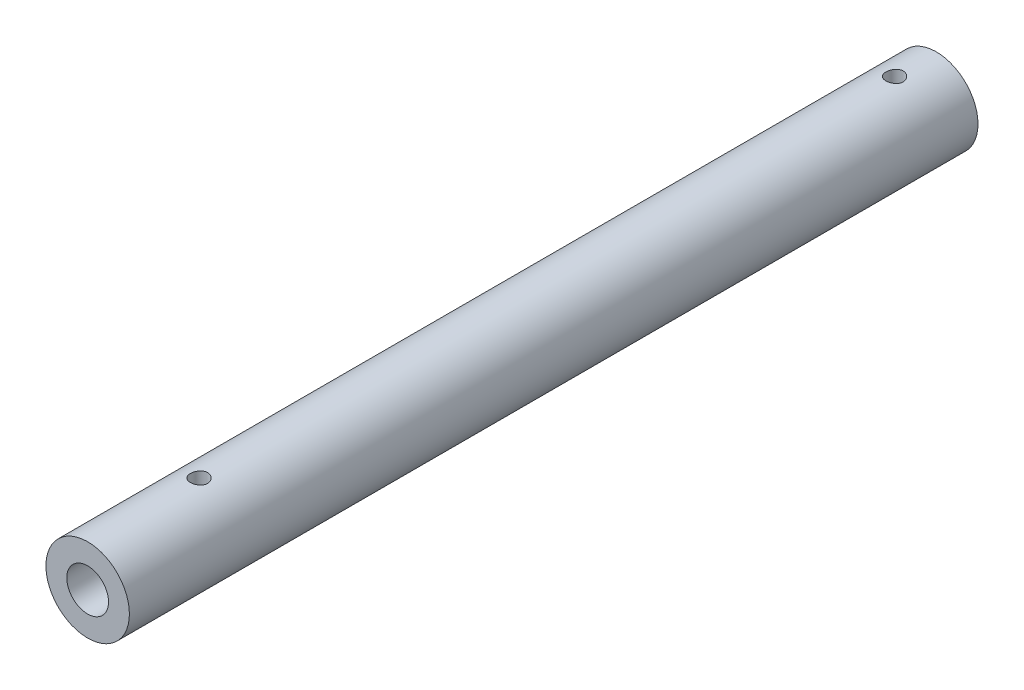
SolidWorks part; units mm, degrees
ref_plane "Front Plane" through (0, 0, 0) normal (0, 0, 1) x (1, 0, 0)
ref_plane "Top Plane" through (0, 0, 0) normal (0, 1, 0) x (1, 0, 0)
ref_plane "Right Plane" through (0, 0, 0) normal (1, 0, 0) x (0, 0, -1)
sketch "Sketch1" plane through (0, 0, 0) normal (0, 0, 1) x (1, 0, 0)
  circle A0 centre (0, 0) radius 15
  circle A1 centre (0, 0) radius 7.5
  dimension "D1" = 30
  dimension "D2" = 7.5
extrude "Boss-Extrude1" add sketch "Sketch1" along normal blind 152.5 and the other way blind 152.5
sketch "Sketch2" plane through (0, 0, 0) normal (0, 1, 0) x (1, 0, 0)
  line L0 (-15, -152.5) -> (15, -152.5) construction
  circle A0 centre (0, -112.5) radius 3.1
  dimension "D1" = 6.2
  dimension "D2" = 40
extrude "Cut-Extrude1" cut sketch "Sketch2" along normal through all
sketch "Sketch3" plane through (0, 0, 0) normal (0, 1, 0) x (1, 0, 0)
  line L0 (15, 152.5) -> (-15, 152.5) construction
  circle A0 centre (0, 137.5) radius 3.1
  dimension "D1" = 6.2
  dimension "D2" = 15
extrude "Cut-Extrude2" cut sketch "Sketch3" along normal through all
